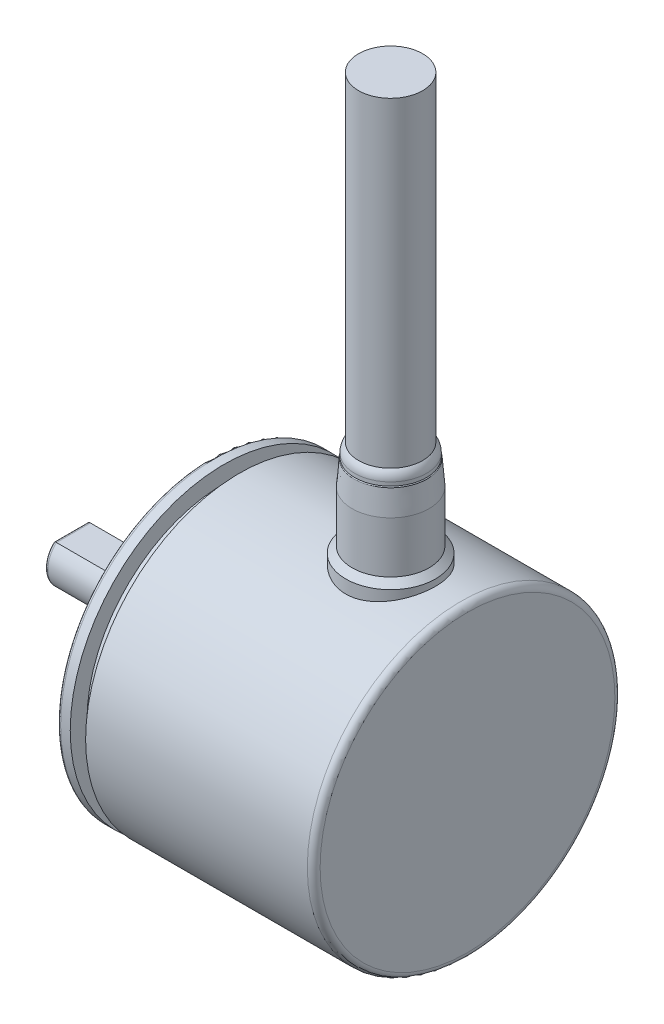
SolidWorks part; units mm, degrees
ref_plane "Plan de face" through (0, 0, 0) normal (0, 0, 1) x (1, 0, 0)
ref_plane "Plan de dessus" through (0, 0, 0) normal (0, 1, 0) x (1, 0, 0)
ref_plane "Plan de droite" through (0, 0, 0) normal (1, 0, 0) x (0, 0, -1)
sketch "Esquisse1" plane through (0, 0, 0) normal (0, 1, 0) x (1, 0, 0)
  line L0 (0, 0) -> (80.3603, 0) construction
  line L1 (12, 10.7) -> (12, 12)
  line L2 (0, 0) -> (31, 0)
  line L3 (0, 0) -> (0, 2)
  line L4 (0, 2) -> (10, 2)
  line L7 (11, 6) -> (11, 12)
  line L8 (11, 12) -> (12, 12)
  line L9 (10, 2) -> (10, 6)
  line L10 (12, 10.7) -> (13.2, 10.7)
  line L11 (10, 6) -> (11, 6)
  line L14 (13.2, 12) -> (31, 12)
  line L15 (13.2, 12) -> (13.2, 10.7)
  line L17 (31, 12) -> (31, 0)
  dimension "D1" = 1
  dimension "D2" = 1.2
  dimension "D3" = 1.3
  dimension "D4" = 20
  dimension "D5" = 6
  dimension "D6" = 10
  dimension "D7" = 1
  dimension "D8" = 2
  dimension "D9" = 12
revolve "Révolution1" add sketch "Esquisse1" angle 360 about L0
sketch "Esquisse2" plane through (0, 0, 0) normal (0, 1, 0) x (1, 0, 0)
  line L0 (31, -12) -> (31, 12) construction
  circle A0 centre (25, 0) radius 3.5
  dimension "D2" = 7
  dimension "D1" = 6
extrude "Boss.-Extru.1" add sketch "Esquisse2" along normal blind 13
sketch "Esquisse3" plane through (0, 13, 0) normal (0, 1, 0) x (1, 0, 0)
  circle A0 centre (25, 0) radius 3
  circle A1 centre (25, 0) radius 3.5 construction
  dimension "D1" = 6
extrude "Boss.-Extru.2" add sketch "Esquisse3" along normal blind 6
sketch "Esquisse4" plane through (0, 19, 0) normal (0, 1, 0) x (1, 0, 0)
  circle A0 centre (25, 0) radius 2.8
  circle A1 centre (25, 0) radius 3 construction
  dimension "D1" = 5.6
extrude "Boss.-Extru.3" add sketch "Esquisse4" along normal blind 1
sketch "Esquisse5" plane through (0, 20, 0) normal (0, 1, 0) x (1, 0, 0)
  circle A0 centre (25, 0) radius 2.5
  circle A1 centre (25, 0) radius 2.8 construction
  dimension "D1" = 5
extrude "Boss.-Extru.4" add sketch "Esquisse5" along normal blind 25
chamfer "Chanfrein1" distance 0.5 angle 45 1 edges at (25, 13, 3.5)
chamfer "Chanfrein2" distance 2 distance2 0.16 1 edges at (25, 19, 3) first distance on face at (25, 19, 3)
fillet "Congé1" radius 1 1 edges at (25, 20, 2.8)
fillet "Congé2" radius 0.1 1 edges at (25, 19, 2.84)
sketch "Esquisse7" plane through (0, 0, 0) normal (-1, 0, 0) x (0, 0, 1)
  line L0 (-1.3229, 1.5) -> (1.3229, 1.5)
  arc A1 (-1.3229, 1.5) -> (1.3229, 1.5) centre (0, 0) cw
  circle A2 centre (0, 0) radius 2 construction
  dimension "D1" = 1.5
extrude "Enlèv. mat.-Extru.2" cut sketch "Esquisse7" against normal blind 8.5
fillet "Congé3" radius 0.5 1 edges at (31, 0, 12)
fillet "Congé4" radius 0.25 2 edges at (10, 0, 6) (11, 0, 12)
fillet "Congé5" radius 0.25 2 edges at (0, 1.5, 0) (0, -2, 0)
sketch "Esquisse9" plane through (10, 0, 0) normal (-1, 0, 0) x (0, 0, 1)
  circle A0 centre (0, 0) radius 5
  circle A1 centre (0, 0) radius 4
  circle A2 centre (0, 0) radius 3
  circle A3 centre (0, 0) radius 2
  circle A5 centre (0, 0) radius 2 construction
  circle M3 centre (0, 0) radius 2
  dimension "D1" = 1
  dimension "D2" = 1
  dimension "D3" = 1
extrude "Enlèv. mat.-Extru.4" cut sketch "Esquisse9" against normal blind 0.25 contours A2 M3 | A0 A1 region at (10, 0, -4.8586) region at (10, 0, -2.9151)
sketch "Esquisse10" plane through (10, 0, 0) normal (-1, 0, 0) x (0, 0, 1)
  circle A0 centre (0, 0) radius 4
  circle A1 centre (0, 0) radius 3
extrude "Enlèv. mat.-Extru.5" cut sketch "Esquisse10" against normal blind 0.5
fillet "Congé6" radius 0.125 2 edges at (10.25, 0, 4) (10.25, 0, 3)
sketch "Esquisse8" plane through (11, 0, 0) normal (-1, 0, 0) x (0, 0, 1)
  circle A0 centre (0, 0) radius 9 construction
  circle A1 centre (0, 9) radius 1.5
  circle A2 centre (7.7942, -4.5) radius 1.5
  circle A3 centre (-7.7942, -4.5) radius 1.5
  circle A4 centre (0, 0) radius 11.75 construction
  dimension "D1" = 18
  dimension "D2" = 3
  dimension "D3" = 3
extrude "Enlèv. mat.-Extru.3" cut sketch "Esquisse8" against normal blind 6
